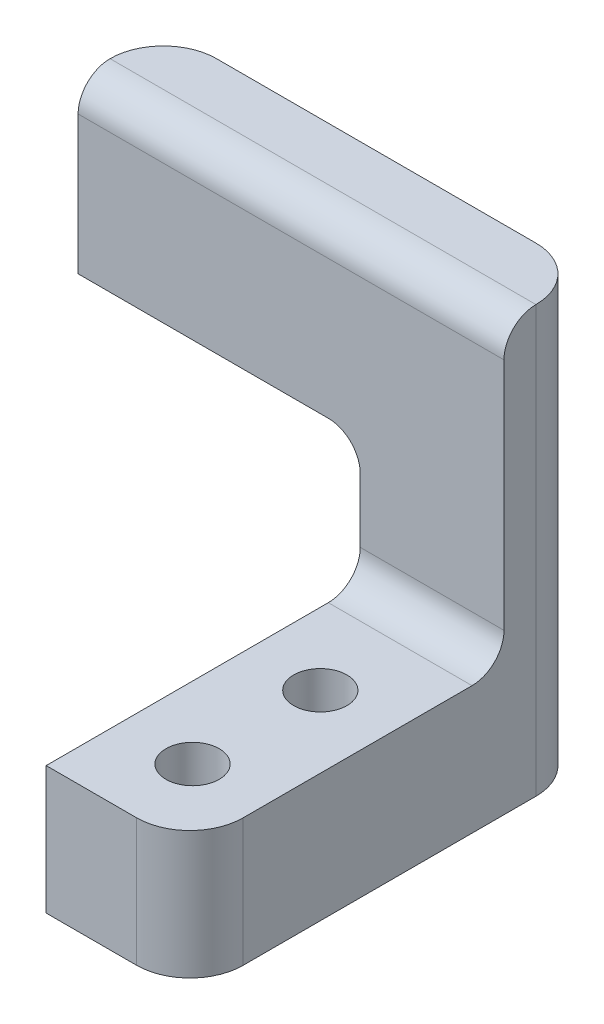
SolidWorks part; units mm, degrees
material "K110"
ref_plane "Front Plane" through (0, 0, 0) normal (0, 0, 1) x (1, 0, 0)
ref_plane "Top Plane" through (0, 0, 0) normal (0, 1, 0) x (1, 0, 0)
ref_plane "Right Plane" through (0, 0, 0) normal (1, 0, 0) x (0, 0, -1)
sketch "Sketch1" plane through (0, 0, 0) normal (0, 1, 0) x (1, 0, 0)
  line L1 (-20, -18.75) -> (20, -18.75)
  line L2 (-20, -18.75) -> (-20, 18.75)
  line L3 (-20, 18.75) -> (20, 18.75)
  line L4 (20, -18.75) -> (20, 18.75)
  line L5 (-20, -18.75) -> (20, 18.75) construction
  line L6 (-20, 18.75) -> (20, -18.75) construction
  point P0 (0, 0)
  dimension "D1" = 37.5
  dimension "D2" = 40
extrude "Boss-Extrude1" add sketch "Sketch1" against normal blind 40
sketch "Sketch2" plane through (20, 0, 0) normal (1, 0, 0) x (0, 0, -1)
  line L0 (18.75, -40) -> (18.75, 0) construction
  line L1 (-18.75, 0) -> (10.75, 0)
  line L2 (-18.75, 0) -> (-18.75, -28)
  line L3 (-18.75, -28) -> (10.75, -28)
  line L4 (10.75, 0) -> (10.75, -28)
  dimension "D1" = 8
  dimension "D2" = 28
extrude "Cut-Extrude1" cut sketch "Sketch2" against normal up to next
fillet "Fillet1" radius 3 2 edges at (0, 0, -10.75) (0, -28, -10.75)
hole_wizard "M6 Tapped Hole1" positions "Sketch12" profile "Sketch4" tap size "M6" standard "ISO" end condition through all
sketch "Sketch12" plane through (0, -40, 0) normal (0, -1, 0) x (-1, 0, 0)
  line L0 (-20, -18.75) -> (-20, 18.75) construction
  line L2 (20, -18.75) -> (-20, -18.75) construction
  point P0 (-13.25, -11.75)
  point P23 (-13.25, 0.25)
  dimension "D1" = 6.75
  dimension "D2" = 7
  dimension "D3" = 12
cosmetic thread "Hole Thread2" parameters "D2"=6
sketch "Sketch4" plane through (13.25, -40, 11.75) normal (1, 0, 0) x (0, 0, -1)
  line L0 (0, 0) -> (0, 40)
  line L1 (0, 40) -> (2.5, 40)
  line L2 (2.5, 40) -> (2.5, 0.525)
  line L3 (2.5, 0.525) -> (3.025, 0)
  line L5 (3.025, 0) -> (0, 0)
  line L6 (-2.5, 0.525) -> (-3.025, 0) construction
  line L11 (0, -6.35) -> (0, 107.95) construction
  dimension "Thru Tap Drill Dia." = 5
  dimension "Thru Tap Drill Depth" = 40
  dimension "Near C'Sink Dia." = 6.05
  dimension "Near C'Sink Angle" = 90
cosmetic thread "Hole Thread3" parameters "D2"=6
fillet "Fillet2" radius 5 4 edges at (20, -20, -18.75) (20, -34, 18.75) (-20, -34, 18.75) (-20, -20, -18.75)
sketch "Sketch7" plane through (0, 0, 0) normal (0, 1, 0) x (1, 0, 0)
  line L0 (-15, -18.75) -> (15, -18.75) construction
  line L1 (-6.5, -18.75) -> (6.5, -18.75)
  line L2 (-6.5, -18.75) -> (-6.5, 10.75)
  line L3 (-6.5, 10.75) -> (6.5, 10.75)
  line L4 (6.5, -18.75) -> (6.5, 10.75)
  line L6 (0, 7.75) -> (0, -18.75) construction
  line L7 (-20, 13.75) -> (20, 13.75) construction
  dimension "D1" = 3
  dimension "13" = 13
extrude "Cut-Extrude2" cut sketch "Sketch7" against normal up to next
sketch "Sketch8" plane through (0, 0, 0) normal (1, 0, 0) x (0, 0, -1)
  line L1 (-18.75, -40) -> (10.75, -40)
  line L2 (-18.75, -40) -> (-18.75, -3)
  line L3 (-18.75, -3) -> (10.75, -3)
  line L4 (10.75, -40) -> (10.75, -3)
extrude "Cut-Extrude3" cut sketch "Sketch8" against normal up to next
sketch "Sketch9" plane through (-20, 0, 0) normal (-1, 0, 0) x (0, 0, 1)
  line L0 (-10.75, -40) -> (-10.75, -3) construction
  line L1 (-18.75, -40) -> (-10.75, -40)
  line L2 (-18.75, -40) -> (-18.75, -16.0022)
  line L3 (-18.75, -16.0022) -> (-10.75, -16.0022)
  line L4 (-10.75, -40) -> (-10.75, -16.0022)
  line L6 (-19.75, -16.0022) -> (-13.75, -16.0022) construction
extrude "Cut-Extrude4" cut sketch "Sketch9" against normal up to surface (26.5 mm away) up to face at (6.5, -32.3243, 1.5257)
fillet "Fillet3" radius 3 1 edges at (6.5, -16.0022, -14.75)
